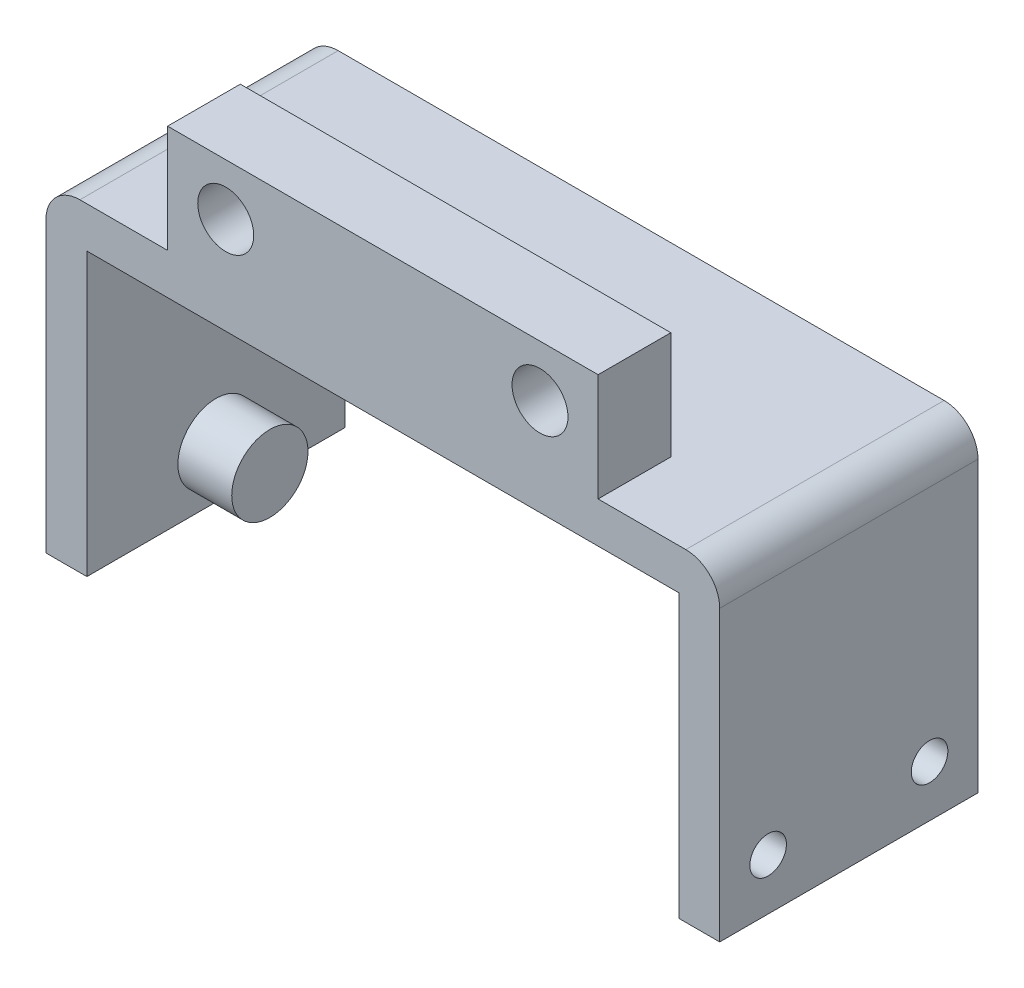
SolidWorks part; units mm, degrees
ref_plane "Front" through (0, 0, 0) normal (0, 0, 1) x (1, 0, 0)
ref_plane "Top" through (0, 0, 0) normal (0, 1, 0) x (1, 0, 0)
ref_plane "Right" through (0, 0, 0) normal (1, 0, 0) x (0, 0, -1)
sketch "Sketch2" plane through (0, 0, 0) normal (1, 0, 0) x (0, 0, -1)
  line L0 (15.24, 38.1) -> (15.24, 0) construction
  line L1 (0, 0) -> (30.48, 0)
  line L2 (0, 0) -> (0, 38.1)
  line L3 (0, 38.1) -> (30.48, 38.1)
  line L4 (30.48, 0) -> (30.48, 38.1)
  circle A0 centre (5.715, 6.05) radius 2.159
  circle A1 centre (24.765, 6.05) radius 2.159
  point P9 (15.24, 6.05)
  dimension "D2" = 4.318
  dimension "D1" = 30.48
  dimension "D3" = 9.525
  dimension "D5" = 38.1
extrude "Boss-Extrude1" add sketch "Sketch2" along normal blind 4.826
sketch "Sketch3" plane through (0, 0, 0) normal (-1, 0, 0) x (0, 0, 1)
  line L1 (-30.48, 38.1) -> (0, 38.1)
  line L2 (-30.48, 38.1) -> (-30.48, 33.274)
  line L3 (-30.48, 33.274) -> (0, 33.274)
  line L4 (0, 38.1) -> (0, 33.274)
  dimension "D1" = 4.826
extrude "Boss-Extrude2" add sketch "Sketch3" along normal blind 74.676
sketch "Sketch4" plane through (0, 33.274, 0) normal (0, -1, 0) x (1, 0, 0)
  line L0 (-74.676, -30.48) -> (0, -30.48) construction
  line L1 (-74.676, 0) -> (-69.85, 0)
  line L2 (-74.676, 0) -> (-74.676, -30.48)
  line L3 (-74.676, -30.48) -> (-69.85, -30.48)
  line L4 (-69.85, 0) -> (-69.85, -30.48)
  dimension "D1" = 4.826
extrude "Boss-Extrude4" add sketch "Sketch4" along normal blind 33.274
sketch "Sketch5" plane through (0, 38.1, 0) normal (0, 1, 0) x (1, 0, 0)
  line L0 (-34.925, 30.48) -> (-34.925, 0) construction
  line L1 (4.826, 30.48) -> (-74.676, 30.48) construction
  line L2 (4.826, 0) -> (-74.676, 0) construction
  line L4 (-60.325, 0) -> (-9.525, 0)
  line L5 (-60.325, 0) -> (-60.325, 8.5819)
  line L6 (-60.325, 8.5819) -> (-9.525, 8.5819)
  line L7 (-9.525, 0) -> (-9.525, 8.5819)
  point P10 (-9.525, 4.2909)
  dimension "D1" = 25.4
  dimension "D2" = 25.4
extrude "Boss-Extrude5" add sketch "Sketch5" along normal blind 12.7
sketch "Sketch6" plane through (0, 0, -8.5819) normal (0, 0, -1) x (-1, 0, 0)
  line L0 (30.8804, 50.8) -> (34.925, 50.8) construction
  line L1 (9.525, 50.8) -> (60.325, 50.8) construction
  line L2 (34.925, 50.8) -> (34.925, 38.1) construction
  line L3 (9.525, 38.1) -> (60.325, 38.1) construction
  circle A0 centre (53.467, 44.704) radius 3.302
  circle A1 centre (16.383, 44.704) radius 3.302
  dimension "D1" = 6.604
  dimension "D2" = 18.542
extrude "Cut-Extrude1" cut sketch "Sketch6" against normal through all contours A1 | A0
fillet "Fillet2" radius 4 2 edges at (-74.676, 38.1, -15.24) (4.826, 38.1, -15.24)
sketch "Sketch7" plane through (-69.85, 0, 0) normal (1, 0, 0) x (0, 0, -1)
  line L0 (30.48, 0) -> (0, 0) construction
  circle A0 centre (15.24, 6.096) radius 4.5
  point P2 (15.24, 6.1202)
  dimension "D1" = 6.096
  dimension "D2" = 9
extrude "Boss-Extrude6" add sketch "Sketch7" along normal blind 6.35
